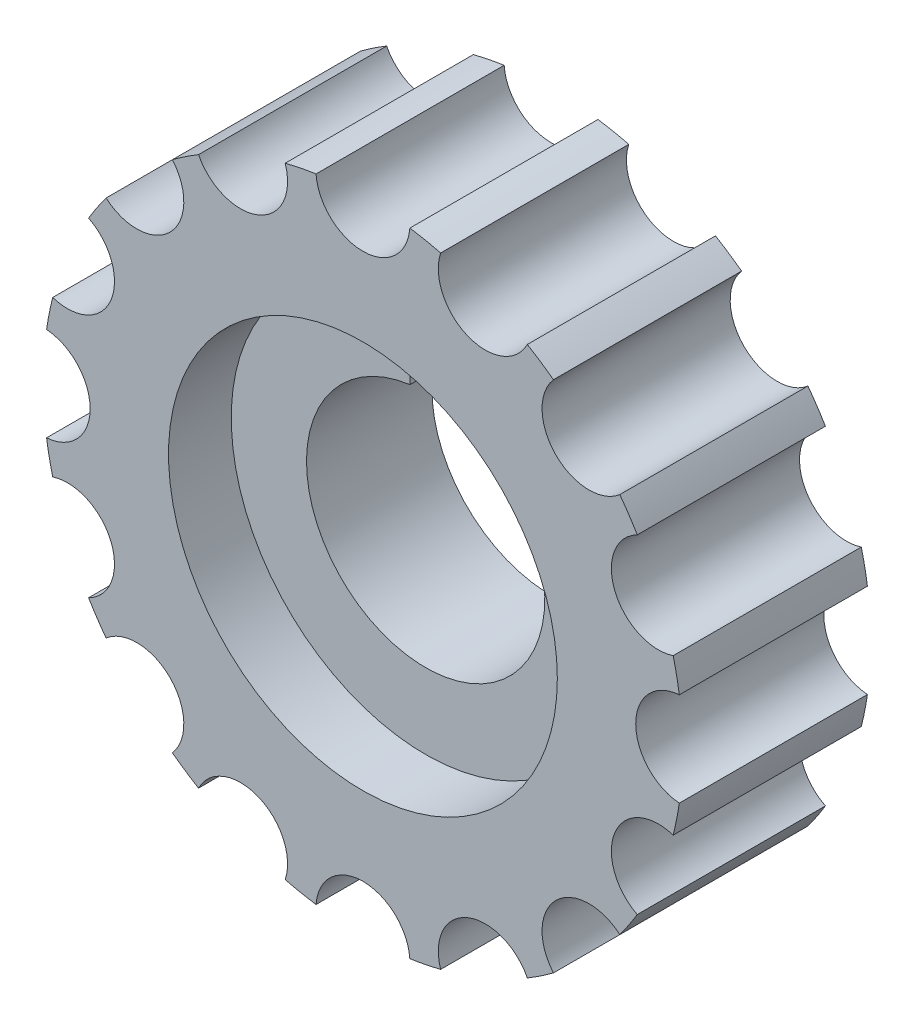
SolidWorks part; units mm, degrees
ref_plane "Front Plane" through (0, 0, 0) normal (0, 0, 1) x (1, 0, 0)
ref_plane "Top Plane" through (0, 0, 0) normal (0, 1, 0) x (1, 0, 0)
ref_plane "Right Plane" through (0, 0, 0) normal (1, 0, 0) x (0, 0, -1)
sketch "Sketch1" plane through (0, 0, 0) normal (0, 0, 1) x (1, 0, 0)
  line L0 (0, 97.8809) -> (0, -97.8809) construction
  line L1 (-121.4847, 0) -> (121.4847, 0) construction
  circle A0 centre (0, 0) radius 51
  arc A1 (-7.4797, 50.4485) -> (7.4797, 50.4485) centre (0, 51) ccw
  circle A2 centre (0, 0) radius 31
  circle A3 centre (0, 0) radius 19
  arc A4 (12.3955, 49.4707) -> (26.2162, 43.746) centre (19.5169, 47.1179) ccw
  arc A5 (30.3836, 40.9614) -> (40.9614, 30.3836) centre (36.0624, 36.0624) ccw
  arc A6 (43.746, 26.2162) -> (49.4707, 12.3955) centre (47.1179, 19.5169) ccw
  arc A7 (50.4485, 7.4797) -> (50.4485, -7.4797) centre (51, 0) ccw
  arc A8 (49.4707, -12.3955) -> (43.746, -26.2162) centre (47.1179, -19.5169) ccw
  arc A9 (40.9614, -30.3836) -> (30.3836, -40.9614) centre (36.0624, -36.0624) ccw
  arc A10 (26.2162, -43.746) -> (12.3955, -49.4707) centre (19.5169, -47.1179) ccw
  arc A11 (7.4797, -50.4485) -> (-7.4797, -50.4485) centre (0, -51) ccw
  arc A12 (-12.3955, -49.4707) -> (-26.2162, -43.746) centre (-19.5169, -47.1179) ccw
  arc A13 (-30.3836, -40.9614) -> (-40.9614, -30.3836) centre (-36.0624, -36.0624) ccw
  arc A14 (-43.746, -26.2162) -> (-49.4707, -12.3955) centre (-47.1179, -19.5169) ccw
  arc A15 (-50.4485, -7.4797) -> (-50.4485, 7.4797) centre (-51, 0) ccw
  arc A16 (-49.4707, 12.3955) -> (-43.746, 26.2162) centre (-47.1179, 19.5169) ccw
  arc A17 (-40.9614, 30.3836) -> (-30.3836, 40.9614) centre (-36.0624, 36.0624) ccw
  arc A18 (-26.2162, 43.746) -> (-12.3955, 49.4707) centre (-19.5169, 47.1179) ccw
  point P5 (0, 0)
  point P6 (0, 0)
  point P62 (0, 0)
  dimension "D1" = 102
  dimension "D2" = 62
  dimension "D3" = 38
  dimension "D4" = 15
  dimension "D5" = 16
extrude "Boss-Extrude1" add sketch "Sketch1" along normal blind 30 contours A18 A0 A17 A16 A15 A14 A13 A12 A11 A10 A9 A8 A7 A6 A5 A4 A1 A2 region at (42.0731, 0, 0)
extrude "Boss-Extrude2" add sketch "Sketch1<3>" along normal blind 20 contours A2 A3 region at (-30.1232, 0, 0)
sketch "Sketch1<3>" plane through (0, 0, 0) normal (0, 0, 1) x (1, 0, 0) same geometry as "Sketch1"
sketch "Sketch3" plane through (0, 0, 0) normal (0, 0, 1) x (1, 0, 0)
  line L0 (0, -2.4504) -> (0, 26.5677) construction
  line L2 (-2.5, 24.7671) -> (2.5, 24.7671)
  line L3 (-2.5, 24.7671) -> (-2.5, 12.7671)
  line L4 (-2.5, 12.7671) -> (2.5, 12.7671)
  line L5 (2.5, 24.7671) -> (2.5, 12.7671)
  line L6 (-2.5, 24.7671) -> (2.5, 12.7671) construction
  line L7 (-2.5, 12.7671) -> (2.5, 24.7671) construction
  point P3 (0, 18.7671)
  point P8 (-2.5, 12.7671)
  point P10 (-2.5, 12.7671)
  dimension "D1" = 12
  dimension "D2" = 5
  dimension "D3" = 24.7671
extrude "Cut-Extrude7" cut sketch "Sketch3" along normal blind 20
